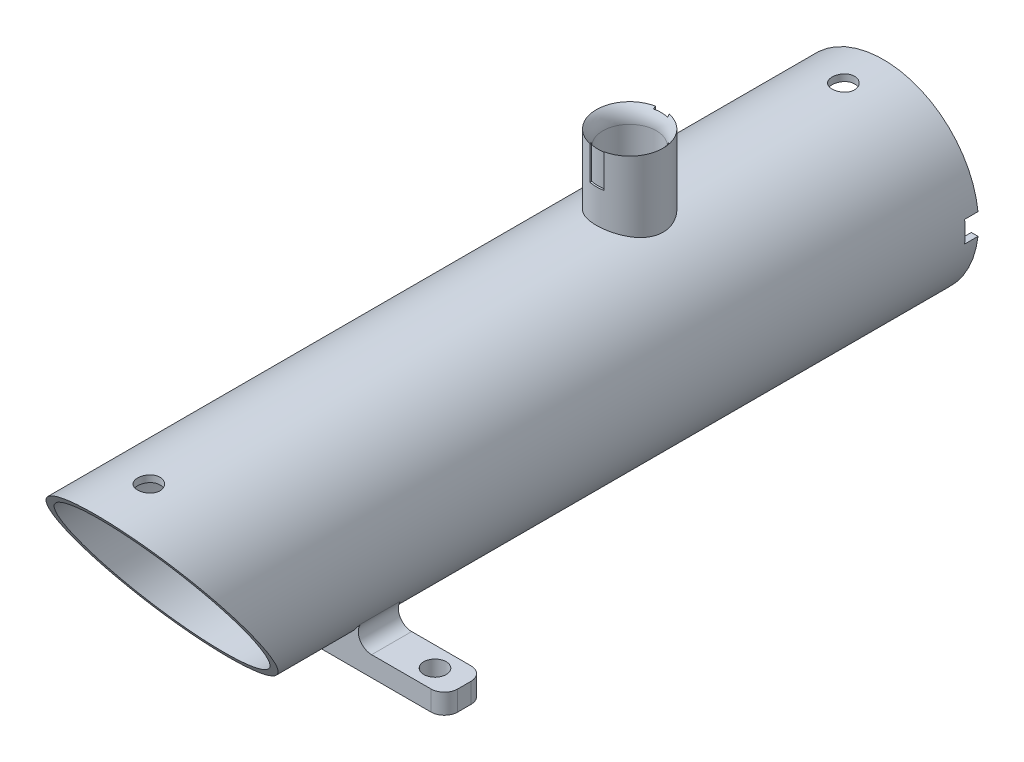
SolidWorks part; units mm, degrees
ref_plane "Front Plane" through (0, 0, 0) normal (0, 0, 1) x (1, 0, 0)
ref_plane "Top Plane" through (0, 0, 0) normal (0, 1, 0) x (1, 0, 0)
ref_plane "Right Plane" through (0, 0, 0) normal (1, 0, 0) x (0, 0, -1)
sketch "Sketch4" plane through (0, 0, 0) normal (0, 0, 1) x (1, 0, 0)
  circle A0 centre (0, 0) radius 14.25
  circle A1 centre (0, 0) radius 13.25
  dimension "D1" = 26.5
  dimension "D2" = 1
extrude "Boss-Extrude3" add sketch "Sketch4" along normal blind 118
sketch "Sketch5" plane through (0, 0, 118) normal (0, 0, 1) x (1, 0, 0)
  circle A0 centre (0, 0) radius 14.25 construction
  point P0 (0, 14.25)
  point P1 (14.25, 0)
  point P4 (-14.25, 0)
  point P5 (0, -14.25)
ref_plane "Plane1" through (0, 14.25, 118) normal (0, 1, 0) x (1, 0, 0)
sketch "Sketch6" plane through (0, 14.25, 118) normal (0, 1, 0) x (1, 0, 0)
  line L0 (-14.25, 0) -> (14.25, 0) construction
  circle A0 centre (0, 80) radius 4
  circle A1 centre (0, 80) radius 5
  dimension "D1" = 8
  dimension "D2" = 1
  dimension "D3" = 80
extrude "Boss-Extrude4" add sketch "Sketch6" along normal blind 10 and the other way blind 4
sketch "Sketch7" plane through (0, 24.25, 0) normal (0, 1, 0) x (1, 0, 0)
  circle A0 centre (0, -38) radius 4
  circle A1 centre (0, -38) radius 4 construction
extrude "Cut-Extrude1" cut sketch "Sketch7" against normal blind 20
sketch "Sketch8" plane through (0, 0, 118) normal (0, 0, 1) x (1, 0, 0)
  circle A0 centre (0, 0) radius 13.25
extrude "Cut-Extrude2" cut sketch "Sketch8" against normal up to surface (118 mm away) up to face at (14.25, 0, 0)
sketch "Sketch11" plane through (0, 14.25, 118) normal (0, 1, 0) x (1, 0, 0)
  line L0 (-14.25, 0) -> (14.25, 0) construction
  line L1 (13.25, 118) -> (-13.25, 118) construction
  circle A0 centre (0, 8) radius 1.675
  circle A1 centre (0, 112) radius 1.675
  dimension "D1" = 3.35
  dimension "D2" = 8
  dimension "D3" = 6
extrude "Cut-Extrude5" cut sketch "Sketch11" against normal blind 13
ref_plane "Plane5" through (0, -14.25, 118) normal (0, -1, 0) x (-1, 0, 0)
sketch "Sketch15" plane through (0, -14.25, 118) normal (0, -1, 0) x (-1, 0, 0)
  line L5 (0, 65) -> (0, 0) construction
  line L7 (0, 28) -> (-24.25, 28)
  line L13 (0, 28) -> (0, 34)
  line L14 (0, 34) -> (-24.25, 34)
  line L15 (-24.25, 28) -> (-24.25, 34)
  line L16 (-14.25, 118) -> (-14.25, 0) construction
  line L17 (-14.25, 0) -> (14.25, 0) construction
  line L18 (-24.25, 31) -> (0, 31) construction
  circle A2 centre (-19.85, 31) radius 1.675
  point P0 (0, 65)
  point P15 (0, 65)
  point P16 (0, 22.5)
  dimension "D4" = 3.35
  dimension "D6" = 5.6
  dimension "D1" = 10
  dimension "D2" = 6
  dimension "D3" = 28
fillet "Fillet2" radius 3 1 edges at (-4, 24.25, 38)
sketch "Sketch20" plane through (0, 14.25, 118) normal (0, 1, 0) x (1, 0, 0)
  line L1 (-1.05, 85) -> (1.05, 85)
  line L2 (-1.05, 85) -> (-1.05, 82)
  line L3 (-1.05, 82) -> (1.05, 82)
  line L4 (1.05, 85) -> (1.05, 82)
  line L5 (-1.05, 78) -> (1.05, 78)
  line L6 (-1.05, 78) -> (-1.05, 75)
  line L7 (-1.05, 75) -> (1.05, 75)
  line L8 (1.05, 78) -> (1.05, 75)
  circle A2 centre (0, 80) radius 5 construction
  circle A3 centre (0, 80) radius 4.7474
  circle A4 centre (0, 80) radius 4 construction
  point P14 (0, 78)
  point P15 (0, 82)
  dimension "D1" = 2.1
  dimension "D2" = 3
extrude "Boss-Extrude8" add sketch "Sketch15" against normal blind 3
sketch "Sketch27" plane through (0, 0, 0) normal (0, 0, -1) x (-1, 0, 0)
  circle A0 centre (0, 0) radius 13.25
extrude "Cut-Extrude15" cut sketch "Sketch27" against normal up to surface (118 mm away) up to face at (14.25, 0, 118)
sketch "Sketch29" plane through (0, 0, 0) normal (0, 0, -1) x (-1, 0, 0)
  line L1 (-17.6299, -1.6) -> (17.6299, -1.6)
  line L2 (-17.6299, -1.6) -> (-17.6299, 1.6)
  line L3 (-17.6299, 1.6) -> (17.6299, 1.6)
  line L4 (17.6299, -1.6) -> (17.6299, 1.6)
  line L5 (-17.6299, -1.6) -> (17.6299, 1.6) construction
  line L6 (-17.6299, 1.6) -> (17.6299, -1.6) construction
  point P0 (0, 0)
  dimension "D1" = 3.2
extrude "Cut-Extrude17" cut sketch "Sketch29" against normal blind 2
extrude "Cut-Extrude18" cut sketch "Sketch20" along normal blind 10 from offset 5 contours A3 L4 L1 L2 | A3 L6 L7 L8 region at (0, 14.25, 33.1479) region at (0, 14.25, 42.8521)
sketch "Sketch30" plane through (24.25, 0, 0) normal (1, 0, 0) x (0, 0, -1)
  line L0 (-118, 14.25) -> (-98.0441, -14.25)
  line L1 (-118, -14.25) -> (-90, -14.25) construction
  line L2 (-98.0441, -14.25) -> (-118, -14.25)
  line L3 (-118, -14.25) -> (-118, 14.25)
  dimension "D1" = 35
extrude "Cut-Extrude19" cut sketch "Sketch30" against normal blind 50
fillet "Fillet3" radius 2 3 edges at (8.7464, -11.25, 87) (24.25, -12.75, 90) (24.25, -12.75, 84)
